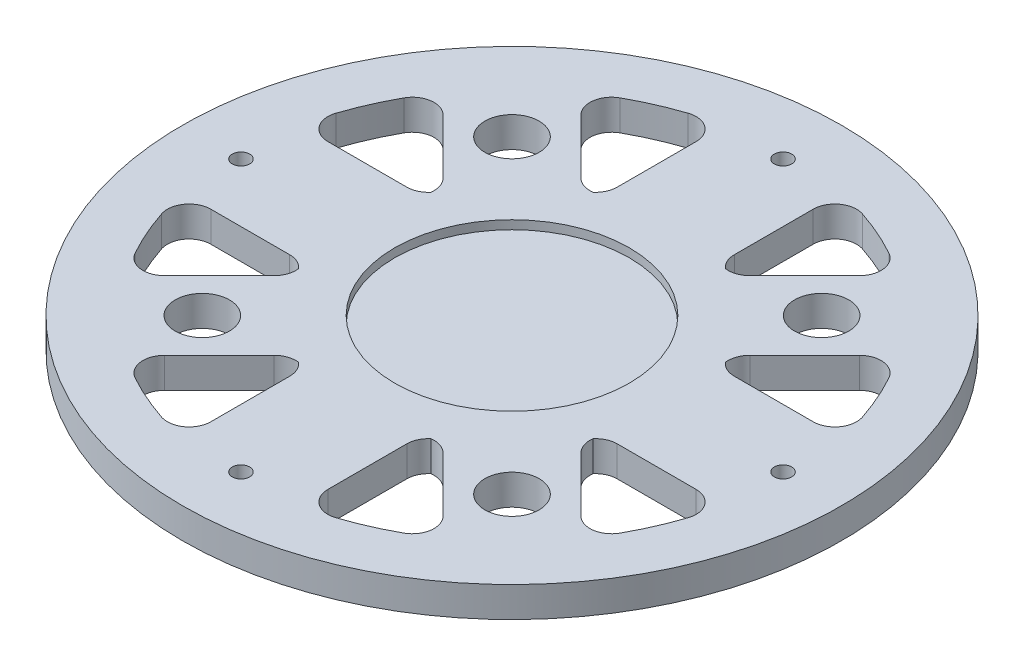
SolidWorks part; units mm, degrees
material "Custom Plastic"
ref_plane "Front Plane" through (0, 0, 0) normal (0, 0, 1) x (1, 0, 0)
ref_plane "Top Plane" through (0, 0, 0) normal (0, 1, 0) x (1, 0, 0)
ref_plane "Right Plane" through (0, 0, 0) normal (1, 0, 0) x (0, 0, -1)
sketch "Sketch1" plane through (0, 0, 0) normal (0, 1, 0) x (1, 0, 0)
  circle A0 centre (0, 0) radius 76
  circle A1 centre (0, 0) radius 27.051
  circle A2 centre (0, 0) radius 62.5 construction
  circle A3 centre (0, 62.5) radius 2
  circle A4 centre (62.5, 0) radius 2
  circle A5 centre (0, -62.5) radius 2
  circle A6 centre (-62.5, 0) radius 2
  dimension "D1" = 152
  dimension "D2" = 54.102
  dimension "D3" = 125
  dimension "D4" = 4
extrude "Boss-Extrude1" add sketch "Sketch1" along normal blind 7
sketch "Sketch3" plane through (0, 0, 0) normal (0, -1, 0) x (1, 0, 0)
  circle A0 centre (0, 0) radius 27.051
extrude "Boss-Extrude2" add sketch "Sketch3" against normal blind 5
sketch "Sketch4" plane through (0, 7, 0) normal (0, 1, 0) x (1, 0, 0)
  line L0 (134.0846, 0) -> (0, 0) construction
  line L1 (0, 0) -> (0, 97.8812) construction
  line L2 (13.5, 62.5) -> (13.5, 34.504)
  line L3 (34.504, 13.5) -> (62.5, 13.5)
  line L4 (-34.504, 13.5) -> (-62.5, 13.5)
  line L5 (-13.5, 62.5) -> (-13.5, 34.504)
  line L6 (34.504, -13.5) -> (62.5, -13.5)
  line L7 (13.5, -62.5) -> (13.5, -34.504)
  line L8 (-13.5, -62.5) -> (-13.5, -34.504)
  line L9 (-34.504, -13.5) -> (-62.5, -13.5)
  line L10 (26.199, 26.199) -> (45.2134, 45.2134)
  line L11 (0, 0) -> (72.917, 72.917) construction
  line L12 (36.5531, 52.463) -> (17.0072, 32.9171)
  line L13 (52.463, 36.5531) -> (32.9171, 17.0072)
  line L14 (36.5531, -52.463) -> (17.0072, -32.9171)
  line L15 (52.463, -36.5531) -> (32.9171, -17.0072)
  line L16 (-52.463, -36.5531) -> (-32.9171, -17.0072)
  line L17 (-36.5531, -52.463) -> (-17.0072, -32.9171)
  line L18 (-52.463, 36.5531) -> (-32.9171, 17.0072)
  line L19 (-36.5531, 52.463) -> (-17.0072, 32.9171)
  arc A0 (13.5, 62.5) -> (62.5, 13.5) centre (0, 0) cw
  circle A1 centre (35.7062, 35.7062) radius 6.25
  circle A2 centre (35.7062, 35.7062) radius 11.25
  circle A5 centre (35.7062, -35.7062) radius 6.25
  arc A7 (-13.5, 62.5) -> (-62.5, 13.5) centre (0, 0) ccw
  arc A8 (13.5, -62.5) -> (62.5, -13.5) centre (0, 0) ccw
  arc A10 (-13.5, -62.5) -> (-62.5, -13.5) centre (0, 0) cw
  circle A11 centre (0, 0) radius 37.051
  circle A12 centre (0, 0) radius 27.051 construction
  circle A13 centre (35.7062, -35.7062) radius 11.25
  circle A14 centre (-35.7062, -35.7062) radius 6.25
  circle A15 centre (-35.7062, -35.7062) radius 11.25
  circle A16 centre (-35.7062, 35.7062) radius 6.25
  circle A17 centre (-35.7062, 35.7062) radius 11.25
  dimension "D1" = 10
  dimension "D4" = 63.9414
  dimension "D6" = 12.5
  dimension "D7" = 5
  dimension "D2" = 27
  dimension "D3" = 27
  dimension "D5" = 45
extrude "Cut-Extrude1" cut sketch "Sketch4" against normal blind 10 contours A11 L7 A8 L14 | A11 L15 A8 L6 | A11 L17 A10 L8 | A11 L9 A10 L16 | A11 L18 A7 L4 | A11 L5 A7 L19 | A11 L12 A0 L2 | A11 L3 A0 L13 | A1 | A5 | A14 | A16 region at (21.5497, 7, -49.012) region at (-21.5497, 7, -49.012) region at (49.012, 7, -21.5497) region at (-49.012, 7, -21.5497) region at (-49.012, 7, 21.5497) region at (49.012, 7, 21.5497) region at (-21.5497, 7, 49.012) region at (21.5497, 7, 49.012)
fillet "Fillet1" radius 5 32 edges at (34.504, 3.5, 13.5) (62.5, 3.5, 13.5) (52.463, 3.5, 36.5531) (32.9171, 3.5, 17.0072) (32.9171, 3.5, -17.0072) (34.504, 3.5, -13.5) (62.5, 3.5, -13.5) (52.463, 3.5, -36.5531) (36.5531, 3.5, -52.463) (13.5, 3.5, -62.5) (13.5, 3.5, -34.504) (17.0072, 3.5, -32.9171) (-17.0072, 3.5, -32.9171) (-36.5531, 3.5, -52.463) (-13.5, 3.5, -34.504) (-13.5, 3.5, -62.5) (-32.9171, 3.5, -17.0072) (-52.463, 3.5, -36.5531) (-62.5, 3.5, -13.5) (-34.504, 3.5, -13.5) (-32.9171, 3.5, 17.0072) (-34.504, 3.5, 13.5) (-62.5, 3.5, 13.5) (-52.463, 3.5, 36.5531) (-36.5531, 3.5, 52.463) (-13.5, 3.5, 62.5) (-13.5, 3.5, 34.504) (-17.0072, 3.5, 32.9171) (17.0072, 3.5, 32.9171) (13.5, 3.5, 34.504) (13.5, 3.5, 62.5) (36.5531, 3.5, 52.463)
